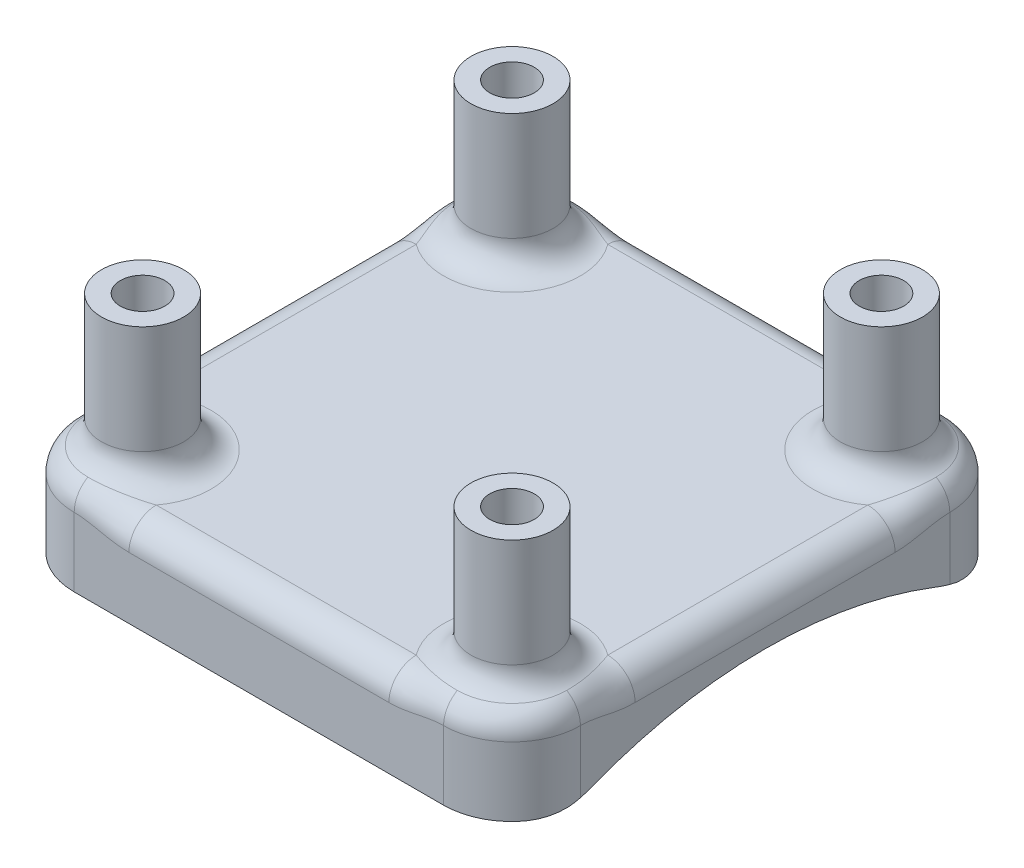
SolidWorks part; units mm, degrees
ref_plane "Front Plane" through (0, 0, 0) normal (0, 0, 1) x (1, 0, 0)
ref_plane "Top Plane" through (0, 0, 0) normal (0, 1, 0) x (1, 0, 0)
ref_plane "Right Plane" through (0, 0, 0) normal (1, 0, 0) x (0, 0, -1)
sketch "Sketch1" plane through (0, 0, 0) normal (0, 1, 0) x (1, 0, 0)
  line L0 (-13.5, -13.5) -> (-13.5, 13.5)
  line L1 (-13.5, -13.5) -> (13.5, -13.5)
  line L2 (-13.5, 13.5) -> (13.5, 13.5)
  line L3 (13.5, -13.5) -> (13.5, 13.5)
  line L4 (-13.5, -13.5) -> (13.5, 13.5) construction
  line L5 (-13.5, 13.5) -> (13.5, -13.5) construction
  circle A0 centre (-13.5, 13.5) radius 1.625
  circle A1 centre (13.5, 13.5) radius 1.625
  circle A2 centre (-13.5, -13.5) radius 1.625
  circle A3 centre (13.5, -13.5) radius 1.625
  circle A4 centre (-13.5, -13.5) radius 3
  circle A5 centre (13.5, -13.5) radius 3
  circle A6 centre (-13.5, 13.5) radius 3
  circle A7 centre (13.5, 13.5) radius 3
  point P1 (0, 0)
  dimension "D3" = 3.25
  dimension "D4" = 3.25
  dimension "D5" = 3.25
  dimension "D6" = 3.25
  dimension "D7" = 6
  dimension "D8" = 6
  dimension "D9" = 6
  dimension "D10" = 6
  dimension "D1" = 27
  dimension "D2" = 27
extrude "Boss-Extrude2" add sketch "Sketch1" against normal blind 10 contours L1 A5 L3 A3 | L3 A5 L1 A3 | L3 A7 L2 A1 | L2 A7 L3 A1 | L2 A6 L0 A0 | L0 A6 L2 A0 | L0 A4 L1 A2 | L1 A4 L0 A2 region at (-14.709, 0, 14.709) region at (-11.9844, 0, 11.9844) region at (-15.5613, 0, -15.5613) region at (-11.9844, 0, -11.9844) region at (11.9844, 0, 11.9844) region at (11.1875, 0, 13.5849) region at (13.5, 0, -16.4151) region at (11.9844, 0, -11.9844)
sketch "Sketch2" plane through (0, -10, 0) normal (0, -1, 0) x (-1, 0, 0)
  line L0 (16.5, -13.5) -> (16.5, 13.5)
  line L1 (13.5, -16.5) -> (-13.5, -16.5)
  line L2 (-16.5, -13.5) -> (-16.5, 13.5)
  line L3 (13.5, 16.5) -> (-13.5, 16.5)
  line L4 (18.5, -13.5) -> (18.5, 13.5)
  line L5 (13.5, 18.5) -> (-13.5, 18.5)
  line L6 (-18.5, -13.5) -> (-18.5, 13.5)
  line L7 (13.5, -18.5) -> (-13.5, -18.5)
  circle A0 centre (13.5, -13.5) radius 3 construction
  circle A1 centre (13.5, 13.5) radius 3 construction
  circle A2 centre (-13.5, -13.5) radius 3 construction
  circle A3 centre (-13.5, 13.5) radius 3 construction
  arc A4 (16.5, -13.5) -> (13.5, -16.5) centre (13.5, -13.5) cw
  arc A5 (-13.5, -16.5) -> (-16.5, -13.5) centre (-13.5, -13.5) cw
  arc A6 (-16.5, 13.5) -> (-13.5, 16.5) centre (-13.5, 13.5) cw
  arc A7 (16.5, 13.5) -> (13.5, 16.5) centre (13.5, 13.5) ccw
  arc A8 (18.5, 13.5) -> (13.5, 18.5) centre (13.5, 13.5) ccw
  arc A9 (-18.5, 13.5) -> (-13.5, 18.5) centre (-13.5, 13.5) cw
  arc A10 (-13.5, -18.5) -> (-18.5, -13.5) centre (-13.5, -13.5) cw
  arc A11 (18.5, -13.5) -> (13.5, -18.5) centre (13.5, -13.5) cw
  circle A12 centre (13.5, -13.5) radius 3
  circle A13 centre (-13.5, -13.5) radius 3
  circle A14 centre (13.5, 13.5) radius 3
  circle A15 centre (-13.5, 13.5) radius 3
  circle M9 centre (13.5, -13.5) radius 3
  dimension "D1" = 2
extrude "Boss-Extrude3" add sketch "Sketch2" along normal blind 3.25 and the other way blind 0.1 contours A11 L4 A8 L5 A9 L6 A10 L7 A7 L0 L1 A5 L2 A6 L3 M9 | A15 L2 A13 L1 L0 A14 L3 M9 region at (0, -10, 0) region at (-16.6655, -10, 16.6655)
sketch "Sketch3" plane through (18.5, 0, 0) normal (1, 0, 0) x (0, 0, -1)
  line L0 (0, 0) -> (0, -13.25)
  line L1 (-13.5, -13.25) -> (13.5, -13.25) construction
  line L2 (0, -13.25) -> (0, -47.75)
  line L3 (0, -9.9) -> (-18.5, -9.9)
  line L4 (-13.5, -9.9) -> (13.5, -9.9) construction
  line L6 (0, -9.9) -> (18.5, -9.9)
  line L7 (18.5, -9.9) -> (18.5, -18.6296)
  line L8 (-18.5, -9.9) -> (-18.5, -18.6296)
  circle A0 centre (0, -47.75) radius 34.5
  arc A2 (-18.5, -18.6296) -> (18.5, -18.6296) centre (0, -47.75) cw
  line M3 (13.5, -9.9) -> (-13.5, -9.9)
  line M4 (-13.5, -9.9) -> (-13.5, -13.25)
  line M5 (-13.5, -13.25) -> (13.5, -13.25)
  line M6 (13.5, -13.25) -> (13.5, -9.9)
  dimension "D1" = 34.5
  dimension "D2" = 18.5
  dimension "D4" = 18.5
extrude "Boss-Extrude4" add sketch "Sketch3" against normal up to surface (37 mm away) contours A0 L3 M5 M4 | L0 M3 M4 M5 | L0 M3 M5 M6 | A0 L7 L6 M6 M5 region at (18.5, -11.575, -6.75) region at (18.5, -11.575, 6.75) region at (18.5, -13.7195, -14.6536) region at (18.5, -13.7195, 14.6536) up to face at (-18.5, -11.575, 0)
extrude "Cut-Extrude1" cut sketch "Sketch2<3>" along normal through all contours A7 A14 | A12 | A13 | A15 region at (-13.5, -10, -13.5)
sketch "Sketch2<3>" plane through (0, -10, 0) normal (0, -1, 0) x (-1, 0, 0) same geometry as "Sketch2"
fillet "Fillet2" radius 5 1 edges at (-18.5, -14.2648, -18.5) type face fillet first side face at (-18.5, -12.9199, 0) second side face at (0, -14.2648, -18.5)
fillet "Fillet3" radius 5 1 edges at (-18.5, -14.2648, 18.5) type face fillet first side face at (-18.5, -12.6203, 2.5811) second side face at (0, -14.2648, 18.5)
fillet "Fillet4" radius 5 1 edges at (18.5, -14.2648, 18.5) type face fillet first side face at (2.5, -14.2648, 18.5) second side face at (18.5, -12.9199, 0)
fillet "Fillet5" radius 5 1 edges at (18.5, -14.2648, -18.5) type face fillet first side face at (18.5, -12.6203, -2.5811) second side face at (2.5, -14.2648, -18.5)
fillet "Fillet8" radius 2 1 edges at (13.5, -9.9, -16.5) type face fillet first side face at (13.5, 0, -10.5) second side face at (-13.5, -9.9, -16.5)
fillet "Fillet9" radius 2 1 edges at (-13.5, -9.9, -16.5) type face fillet first side face at (-13.5, 0, -10.5) second side face at (-13.5, -9.9, -16.5)
fillet "Fillet10" radius 2 1 edges at (-13.5, -9.9, 10.5) type face fillet first side face at (-13.5, 0, 16.5) second side face at (13.5, -9.9, 10.5)
fillet "Fillet11" radius 2 1 edges at (13.5, -9.9, 10.5) type face fillet first side face at (13.5, 0, 16.5) second side face at (13.5, -9.9, 10.5)
ref_plane "Plane1" through (0, -16.4, 0) normal (0, 1, 0) x (1, 0, 0)
sketch "Sketch4" plane through (0, -16.4, 0) normal (0, 1, 0) x (1, 0, 0)
  circle A0 centre (0, 0) radius 35.9607
extrude "Cut-Extrude2" cut sketch "Sketch4" against normal through all
fillet "Fillet12" radius 2 1 edges at (-18.5, -9.9, 0) type face fillet first side face at (0, -9.9, 0) second side face at (-18.5, -12.2627, 0)
fillet "Fillet13" radius 12 3 edges at (-17.3895, -16.4, -14.4023) (0, -16.4, -14.4023) (17.3895, -16.4, -14.4023) type face fillet first side face at (0, -16.4, -16.1737) second side face at (-0.067, -15.8988, -0.7469)
fillet "Fillet14" radius 12 3 edges at (17.3895, -16.4, 14.4023) (0, -16.4, 14.4023) (-17.3895, -16.4, 14.4023) type face fillet first side face at (0, -16.4, 16.1737) second side face at (-0.0707, -15.6822, 1.6295)
